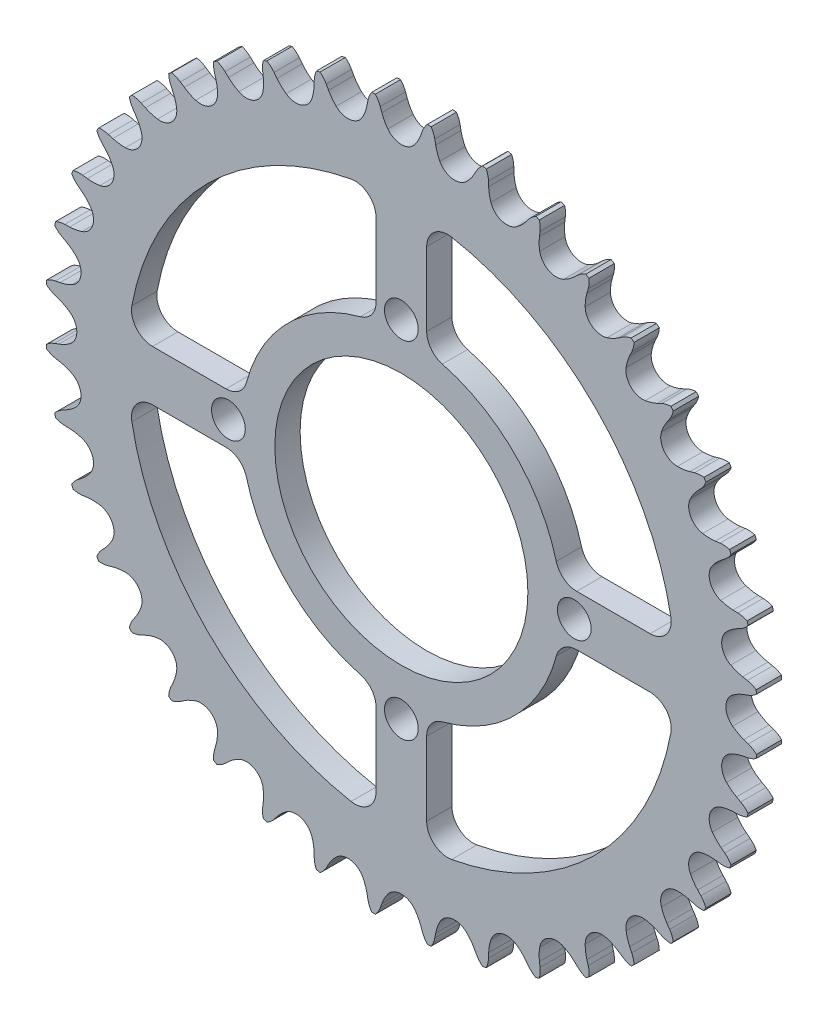
SolidWorks part; units mm, degrees
ref_plane "Plan de face" through (0, 0, 0) normal (0, 0, 1) x (1, 0, 0)
ref_plane "Plan de dessus" through (0, 0, 0) normal (0, 1, 0) x (1, 0, 0)
ref_plane "Plan de droite" through (0, 0, 0) normal (1, 0, 0) x (0, 0, -1)
sketch "Master Sk" plane through (0, 0, 0) normal (0, 0, 1) x (1, 0, 0)
  line L0 (0, 0) -> (0, 80.9339) construction
  line L1 (0, 0) -> (-12.6609, 79.9375) construction
  line L2 (0, 80.9339) -> (-12.6609, 79.9375) construction
  line L3 (0, 80.9339) -> (-3.9899, 80.9339) construction
  line L4 (0, 80.9339) -> (-3.2073, 78.5606) construction
  line L5 (0, 80.9339) -> (5.1061, 84.7122) construction
  line L6 (5.1061, 84.7122) -> (-4.6182, 81.1921) construction
  line L7 (-6.3304, 80.4357) -> (-6.663, 84.662) construction
  line L8 (-4.6182, 81.1921) -> (-5.8949, 84.7189) construction
  line L9 (0, 80.9339) -> (-11.0817, 80.0617) construction
  line L10 (-11.0817, 80.0617) -> (-5.0053, 82.2614) construction
  line L11 (-8.1399, 80.9149) -> (-7.4306, 84.598) construction
  line L12 (-8.1399, 80.9149) -> (-7.9248, 82.0316)
  line L13 (-4.6182, 81.1921) -> (-5.0053, 82.2614)
  circle A2 centre (0, 80.9339) radius 3.97 construction
  circle A6 centre (0, 80.9339) radius 3.9899 construction
  arc A7 (0, 76.944) -> (-3.2073, 78.5606) centre (0, 80.9339) cw
  arc A8 (-4.6182, 81.1921) -> (-3.2073, 78.5606) centre (5.1061, 84.7122) ccw
  circle A9 centre (0, 0) radius 84.9237 construction
  circle A10 centre (-11.0817, 80.0617) radius 6.4623 construction
  circle A11 centre (0, 80.9339) radius 6.4623 construction
  arc A12 (-8.1399, 80.9149) -> (-9.1218, 78.0952) centre (-18.2951, 82.8705) cw
  arc A13 (-12.0367, 75.9967) -> (-9.1218, 78.0952) centre (-12.6609, 79.9375) ccw
  arc A14 (0, 76.944) -> (-12.0367, 75.9967) centre (0, 0) ccw
  arc A15 (-6.663, 84.662) -> (-5.0053, 82.2614) centre (-10.4006, 80.3083) cw
  arc A16 (-6.663, 84.662) -> (-7.9248, 82.0316) centre (-2.2905, 80.9466) ccw
  arc A17 (-15.5182, 75.3629) -> (4.9541, 76.7844) centre (0, 0) ccw construction
  arc A18 (-12.0367, 75.9967) -> (-15.5182, 75.3629) centre (0, 0) ccw construction
  arc A19 (4.9541, 76.7844) -> (0, 76.944) centre (0, 0) ccw construction
  dimension "D3" = 7.94
  dimension "D4" = 7.9797
  dimension "D9" = 10.3419
  dimension "D1" = 12.7
  dimension "D2" = 9
  dimension "D5" = 36.5
  dimension "D6" = 6.352
  dimension "D7" = 16.6
  dimension "D8" = 10.3419
  dimension "D10" = 11.116
sketch "Esquisse2" plane through (0, 0, 0) normal (0, 0, 1) x (1, 0, 0)
  circle A1 centre (0, 0) radius 76.944
  arc A2 (-15.5182, 75.3629) -> (4.9541, 76.7844) centre (0, 0) ccw construction
extrude "Boss.-Extru.1" add sketch "Esquisse2" along normal blind 6
sketch "Esquisse3" plane through (0, 0, 6) normal (0, 0, 1) x (1, 0, 0)
  line L2 (-7.9248, 82.0316) -> (-8.1399, 80.9149)
  line L3 (-4.6182, 81.1921) -> (-5.0053, 82.2614)
  line L4 (-7.9248, 82.0316) -> (-8.1399, 80.9149)
  line L5 (-4.6182, 81.1921) -> (-5.0053, 82.2614)
  arc A7 (-6.663, 84.662) -> (-7.9248, 82.0316) centre (-2.2905, 80.9466) ccw
  arc A8 (-5.0053, 82.2614) -> (-6.663, 84.662) centre (-10.4006, 80.3083) ccw
  arc A9 (-4.6182, 81.1921) -> (-3.2073, 78.5606) centre (5.1061, 84.7122) ccw
  arc A10 (-3.2073, 78.5606) -> (0, 76.944) centre (0, 80.9339) ccw
  arc A11 (0, 76.944) -> (-12.0367, 75.9967) centre (0, 0) ccw
  arc A12 (-12.0367, 75.9967) -> (-9.1218, 78.0952) centre (-12.6609, 79.9375) ccw
  arc A13 (-9.1218, 78.0952) -> (-8.1399, 80.9149) centre (-18.2951, 82.8705) ccw
  arc A14 (-6.663, 84.662) -> (-7.9248, 82.0316) centre (-2.2905, 80.9466) ccw
  arc A15 (-5.0053, 82.2614) -> (-6.663, 84.662) centre (-10.4006, 80.3083) ccw
  arc A16 (-4.6182, 81.1921) -> (-3.2073, 78.5606) centre (5.1061, 84.7122) ccw
  arc A17 (-3.2073, 78.5606) -> (0, 76.944) centre (0, 80.9339) ccw
  arc A18 (0, 76.944) -> (-12.0367, 75.9967) centre (0, 0) ccw
  arc A19 (-12.0367, 75.9967) -> (-9.1218, 78.0952) centre (-12.6609, 79.9375) ccw
  arc A20 (-9.1218, 78.0952) -> (-8.1399, 80.9149) centre (-18.2951, 82.8705) ccw
  dimension "D1" = 0
extrude "Boss.-Extru.2" add sketch "Esquisse3" against normal up to surface (6 mm away) up to face at (76.944, 0, 0)
ref_axis "Axe1" through (0, 0, 6) along (0, 0, -1)
pattern_circular "Répétition circulaire1" count 40 over 360 about axis through (0, 0, 6) along (0, 0, -1) of "Boss.-Extru.2"
sketch "Esquisse4" plane through (0, 0, 6) normal (0, 0, 1) x (1, 0, 0)
  line L0 (0, 0) -> (0, 41) construction
  circle A0 centre (0, 0) radius 30
  circle A1 centre (0, 41) radius 4
  dimension "D1" = 60
  dimension "D3" = 8
  dimension "D2" = 41
extrude "Enlèv. mat.-Extru.1" cut sketch "Esquisse4" against normal through all
pattern_circular "Répétition circulaire2" count 4 over 360 about axis through (0, 0, 0) along (0, 0, 1) of "Enlèv. mat.-Extru.1"
sketch "Esquisse5" plane through (0, 0, 0) normal (0, 0, -1) x (-1, 0, 0)
  line L0 (0, 0) -> (0, 64.8709) construction
  line L1 (0, 0) -> (58.7515, 58.7515) construction
  line L2 (6, 41.5692) -> (6, 58.983)
  line L3 (41.5692, 6) -> (58.983, 6)
  arc A0 (9.7209, 36.7356) -> (36.7356, 9.7209) centre (0, 0) cw
  arc A1 (11.9167, 63.8983) -> (63.8983, 11.9167) centre (0, 0) cw
  arc A2 (41.5692, 6) -> (36.7356, 9.7209) centre (41.5692, 11) cw
  arc A3 (0, 65) -> (6, 64.7225) centre (0, 0) cw construction
  arc A4 (0, 65) -> (45.9619, 45.9619) centre (0, 0) cw construction
  arc A5 (0, 38) -> (6, 37.5233) centre (0, 0) cw construction
  arc A6 (0, 38) -> (26.8701, 26.8701) centre (0, 0) cw construction
  arc A7 (58.983, 6) -> (63.8983, 11.9167) centre (58.983, 11) ccw
  arc A8 (6, 58.983) -> (11.9167, 63.8983) centre (11, 58.983) cw
  arc A9 (6, 41.5692) -> (9.7209, 36.7356) centre (11, 41.5692) ccw
  point P15 (37.5233, 6)
  point P18 (64.7225, 6)
  dimension "D2" = 38
  dimension "D5" = 5
  dimension "D1" = 45
  dimension "D4" = 12
  dimension "D3" = 27
extrude "Enlèv. mat.-Extru.2" cut sketch "Esquisse5" against normal through all
pattern_circular "Répétition circulaire3" count 4 over 360 about axis through (0, 0, 6) along (0, 0, -1) of "Enlèv. mat.-Extru.2"
sketch "Esquisse6" plane through (0, 0, 0) normal (0, 0, -1) x (-1, 0, 0)
  circle A0 centre (0, 0) radius 84.4237
  circle A1 centre (0, 0) radius 84.9237
  dimension "D1" = 0.5
extrude "Enlèv. mat.-Extru.3" cut sketch "Esquisse6" against normal through all
equation "\"pitch\"= 12.7'Pas"
equation "\"Z\"= 40'Nb de dents"
equation "\"Roller\"= 7.94'Roller diam"
equation "\"D1@Master Sk\" = \"pitch\""
equation "\"D2@Master Sk\" = 360 / \"Z\""
equation "\"D3@Master Sk\" = \"Roller\""
equation "\"HubSeat\"= 1.005 * \"Roller\"'HubSeat"
equation "\"D4@Master Sk\" = \"HubSeat\""
equation "\"A\"= 35 + ( 60 / \"Z\" )'Cote A"
equation "\"D5@Master Sk\" = \"A\""
equation "\"R1\"= \"HubSeat\" / 2'Demi HubSeat"
equation "\"oc\"= \"Roller\" * 0.8'ref oc"
equation "\"D6@Master Sk\" = \"oc\""
equation "\"R2\"= 18 - ( 56 / \"Z\" )'ref r2"
equation "\"D7@Master Sk\" = \"R2\""
equation "\"D8@Master Sk\" = \"R1\" + \"oc\""
equation "\"D10@Master Sk\" = \"Roller\" * 1.4"
equation "\"R2_2\"= \"R1\" + \"oc\""
equation "\"D9@Master Sk\" = \"R2_2\""
equation "\"Ep\"= 6'épaisseur pignon"
equation "\"D1@Boss.-Extru.1\"=\"Ep\""
equation "\"D1@Répétition circulaire1\"=\"Z\""
